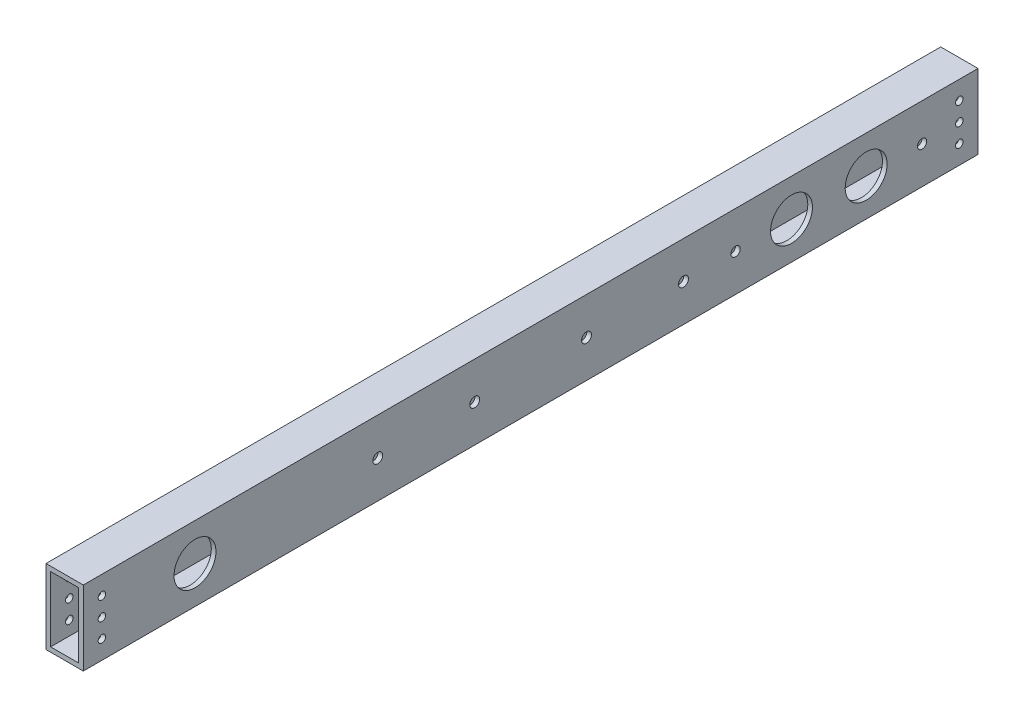
SolidWorks part; units mm, degrees
material "6061-T6 (SS)"
ref_plane "Front Plane" through (0, 0, 0) normal (0, 0, 1) x (1, 0, 0)
ref_plane "Top Plane" through (0, 0, 0) normal (0, 1, 0) x (1, 0, 0)
ref_plane "Right Plane" through (0, 0, 0) normal (1, 0, 0) x (0, 0, -1)
sketch "Sketch1" plane through (0, 0, 0) normal (0, 0, 1) x (1, 0, 0)
  line L0 (-9.525, 22.225) -> (9.525, 22.225)
  line L1 (-12.7, 25.4) -> (12.7, 25.4)
  line L2 (-12.7, 25.4) -> (-12.7, -25.4)
  line L3 (-12.7, -25.4) -> (12.7, -25.4)
  line L4 (12.7, 25.4) -> (12.7, -25.4)
  line L5 (-12.7, 25.4) -> (12.7, -25.4) construction
  line L6 (-12.7, -25.4) -> (12.7, 25.4) construction
  line L7 (9.525, 22.225) -> (9.525, -22.225)
  line L8 (-9.525, -22.225) -> (9.525, -22.225)
  line L9 (-9.525, 22.225) -> (-9.525, -22.225)
  point P0 (0, 0)
  dimension "D1" = 50.8
  dimension "D2" = 25.4
  dimension "D3" = 3.175
extrude "Boss-Extrude1" add sketch "Sketch1" along normal mid plane 609.6
hole_wizard "#10 Clearance Hole1" positions "Sketch4" profile "Sketch3" hole size "#10" standard "ANSI Inch" end condition through all
sketch "Sketch4" plane through (12.7, 0, 0) normal (1, 0, 0) x (0, 0, -1)
  line L0 (-304.8, 25.4) -> (304.8, 25.4) construction
  line L1 (-304.8, -25.4) -> (-304.8, 25.4) construction
  point P0 (-292.1, 12.7)
  point P13 (-292.1, 0)
  point P14 (-292.1, -12.7)
  dimension "D2" = 12.7
  dimension "D3" = 12.7
  dimension "D1" = 3
sketch "Sketch3" plane through (12.7, 12.7, 292.1) normal (0, 1, 0) x (0, 0, -1)
  line L0 (0, 0) -> (0, 25.4)
  line L1 (0, 25.4) -> (2.5527, 25.4)
  line L2 (2.5527, 25.4) -> (2.5527, 0)
  line L5 (2.5527, 0) -> (0, 0)
  line L11 (0, -6.35) -> (0, 107.95) construction
  dimension "Thru Hole Dia." = 5.1054
  dimension "Thru Hole Depth" = 25.4
mirror "Mirror1" about plane through (0, 0, 0) normal (0, 0, 1) of "#10 Clearance Hole1"
hole_wizard "1/4 Clearance Hole2" positions "Sketch6" profile "Sketch5" hole size "1/4" standard "ANSI Inch" end condition through all
sketch "Sketch6" plane through (12.7, 0, 0) normal (1, 0, 0) x (0, 0, -1)
  line L0 (-38.1, 0) -> (38.1, 0) construction
  point P0 (-38.1, 0)
  point P2 (38.1, 0)
  point P13 (-104.14, 0)
  point P15 (104.14, 0)
  dimension "D1" = 76.2
  dimension "D2" = 66.04
  dimension "D3" = 66.04
sketch "Sketch5" plane through (12.7, 0, 38.1) normal (0, 1, 0) x (0, 0, -1)
  line L0 (0, 0) -> (0, 25.4)
  line L1 (0, 25.4) -> (3.3782, 25.4)
  line L2 (3.3782, 25.4) -> (3.3782, 0)
  line L5 (3.3782, 0) -> (0, 0)
  line L11 (0, -6.35) -> (0, 107.95) construction
  dimension "Thru Hole Dia." = 6.7564
  dimension "Thru Hole Depth" = 25.4
sketch "Sketch7" plane through (12.7, 0, 0) normal (1, 0, 0) x (0, 0, -1)
  line L0 (304.8, -25.4) -> (304.8, 25.4) construction
  line L2 (139.6238, 0) -> (266.7, 0) construction
  line L3 (279.4, -25.4) -> (279.4, 25.4) construction
  line L4 (-304.8, -25.4) -> (304.8, -25.4) construction
  line L5 (-304.8, 25.4) -> (304.8, 25.4) construction
  circle A0 centre (-228.6762, 0) radius 14.2875
  circle A1 centre (177.7238, 0) radius 14.2875
  circle A2 centre (228.6, 0) radius 14.2875
  circle A3 centre (177.7238, 0) radius 26.67 construction
  circle A4 centre (228.6, 0) radius 26.67 construction
  circle A5 centre (139.6238, 0) radius 3.175
  circle A6 centre (266.7, 0) radius 3.175
  circle A7 centre (139.6238, 0) radius 6.35 construction
  dimension "D1" = 28.575
  dimension "D2" = 28.575
  dimension "D7" = 53.34
  dimension "D8" = 6.35
  dimension "D12" = 12.7
  dimension "D5" = 406.4
  dimension "D3" = 50.8762
  dimension "D4" = 76.2
  dimension "D9" = 38.1
  dimension "D10" = 38.1
  dimension "D11" = 127.0762
  dimension "D13" = 25.4
extrude "Cut-Extrude1" cut sketch "Sketch7" against normal through all
